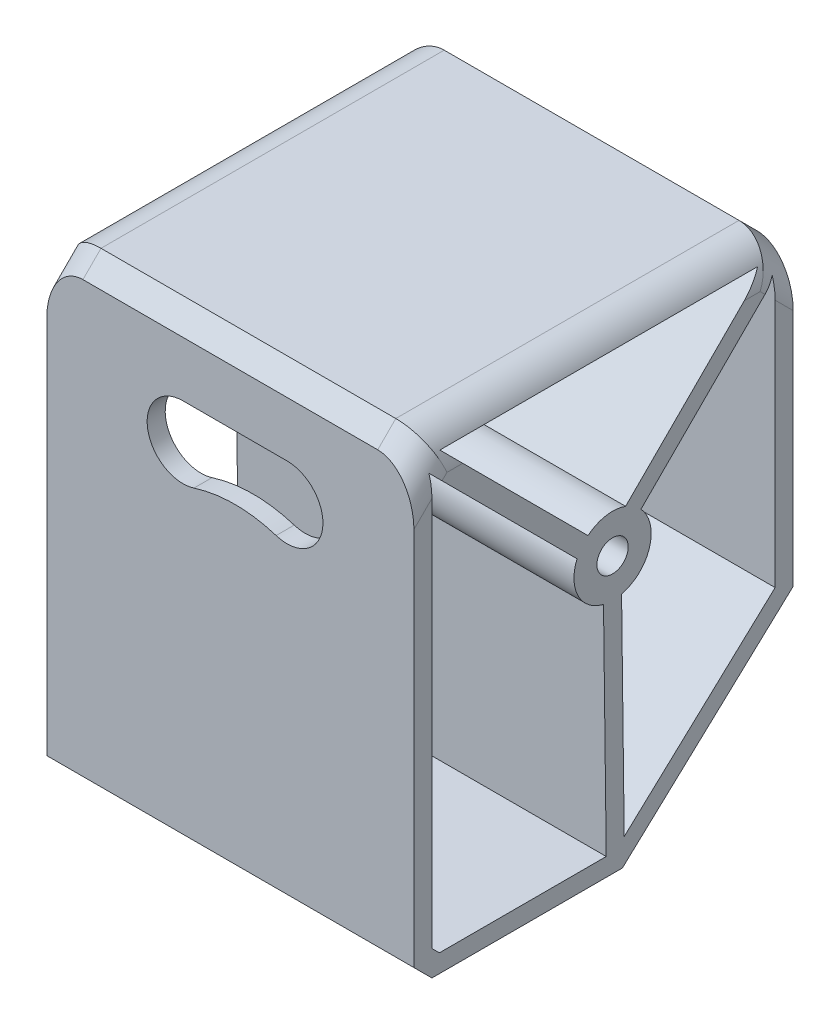
SolidWorks part; units mm, degrees
ref_plane "Front Plane" through (0, 0, 0) normal (0, 0, 1) x (1, 0, 0)
ref_plane "Top Plane" through (0, 0, 0) normal (0, 1, 0) x (1, 0, 0)
ref_plane "Right Plane" through (0, 0, 0) normal (1, 0, 0) x (0, 0, -1)
sketch "Sketch1" plane through (0, 0, 0) normal (1, 0, 0) x (0, 0, -1)
  line L0 (0, 248.2327) -> (10, 258.2327)
  line L1 (10, 0) -> (115.4308, 0)
  line L2 (0, 10) -> (0, 248.2327)
  line L3 (10, 258.2327) -> (200, 258.2327)
  line L4 (210, 87.8057) -> (210, 248.2327)
  line L5 (200, 258.2327) -> (210, 248.2327)
  line L6 (0, 10) -> (10, 0)
  line L7 (115.4308, 0) -> (210, 87.8057)
  line L9 (17.0711, 248.2327) -> (192.9289, 248.2327)
  line L11 (200, 92.1667) -> (200, 241.1617)
  line L12 (116.4476, 14.5898) -> (200, 92.1667)
  line L13 (14.1421, 10) -> (106.5038, 10)
  line L14 (10, 14.1421) -> (14.1421, 10)
  line L15 (10, 14.1421) -> (10, 241.1617)
  line L18 (116.4476, 14.5898) -> (114.9996, 131.0792)
  line L19 (106.5038, 10) -> (105.0004, 130.9549)
  line L20 (105.0004, 130.9549) -> (105.0004, 131.6097)
  line L22 (114.9996, 131.0792) -> (114.9996, 131.6097)
  line L26 (111.5042, 10) -> (200, 92.1667) construction
  line L27 (14.1421, 10) -> (111.5042, 10) construction
  line L30 (10, 241.1617) -> (89.4051, 161.7566)
  line L31 (17.0711, 248.2327) -> (96.4017, 168.9021)
  line L32 (14.1421, 248.2327) -> (195.8579, 248.2327) construction
  line L33 (192.9289, 248.2327) -> (118.3842, 173.688)
  line L34 (200, 241.1617) -> (125.7265, 166.8882)
  line L35 (118.3842, 173.688) -> (117.2225, 172.5263)
  line L36 (89.4051, 161.7566) -> (90.3437, 160.8179)
  line L37 (200, 92.1667) -> (200, 244.0906) construction
  line L38 (10, 14.1421) -> (10, 244.0906) construction
  line L40 (195.8579, 248.2327) -> (200, 244.0906) construction
  line L41 (10, 244.0906) -> (14.1421, 248.2327) construction
  circle A0 centre (110, 152.4) radius 8.6563
  arc A1 (114.9996, 131.6097) -> (125.7265, 166.8882) centre (110, 152.4) ccw
  arc A2 (90.3437, 160.8179) -> (105.0004, 131.6097) centre (110, 152.4) ccw
  arc A3 (117.2225, 172.5263) -> (96.4017, 168.9021) centre (110, 152.4) ccw
  point P0 (0, 0)
  point P1 (210, 258.2327)
  point P2 (0, 258.2327)
  point P3 (200.5236, 84.6121)
  dimension "D1" = 120
  dimension "D10" = 17.3127
  dimension "D8" = 10
  dimension "D3" = 10
  dimension "D2" = 10
  dimension "D6" = 110
  dimension "D7" = 190
  dimension "D9" = 152.4
  dimension "D11" = 10
extrude "Boss-Extrude1" add sketch "Sketch1" along normal blind 203.2
ref_plane "Plane1" through (203.2, 172.5263, -117.2225) normal (-1, 0, 0) x (0, 0, 1)
sketch "Sketch4" plane through (0, 0, 0) normal (0, 0, 1) x (1, 0, 0)
  line L0 (75.4092, 217.8021) -> (133.0074, 217.8021)
  arc A0 (75.4092, 217.8021) -> (81.4563, 179.012) centre (75.4092, 197.9357) ccw
  arc A1 (126.9603, 179.012) -> (133.0074, 217.8021) centre (133.0074, 197.9357) ccw
  arc A2 (126.9603, 179.012) -> (81.4563, 179.012) centre (104.2083, 107.8128) ccw
  point P1 (133.0074, 217.8021)
extrude "Cut-Extrude1" cut sketch "Sketch4" against normal blind 10
fillet "Fillet1" radius 20 6 edges at (203.2, 253.2327, -205) (0, 253.2327, -205) (0, 253.2327, -5) (203.2, 253.2327, -5) (203.2, 258.2327, -105) (0, 258.2327, -105)
